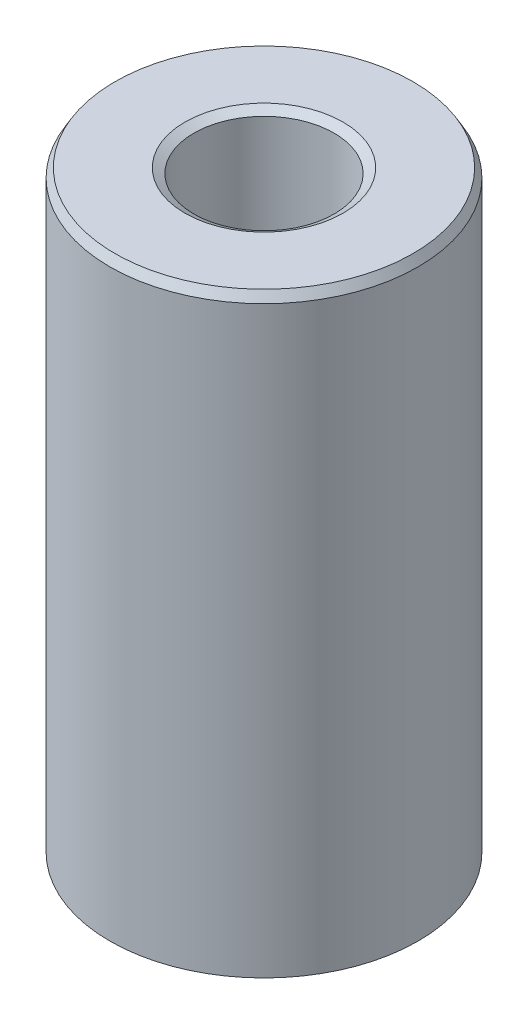
SolidWorks part; units mm, degrees
ref_plane "Front Plane" through (0, 0, 0) normal (0, 0, 1) x (1, 0, 0)
ref_plane "Top Plane" through (0, 0, 0) normal (0, 1, 0) x (1, 0, 0)
ref_plane "Right Plane" through (0, 0, 0) normal (1, 0, 0) x (0, 0, -1)
sketch "Sketch1" plane through (0, 0, 0) normal (0, 1, 0) x (1, 0, 0)
  circle A0 centre (0, 0) radius 60
  dimension "SLEEVE_OD" = 120
extrude "Boss-Extrude1" add sketch "Sketch1" along normal blind 232.8136
sketch "Sketch2" plane through (0, 0, 0) normal (0, 1, 0) x (1, 0, 0)
  circle A0 centre (0, 0) radius 27.3008
  dimension "BORE_D" = 54.6017
extrude "Cut-Extrude1" cut sketch "Sketch2" along normal through all
chamfer "Chamfer1" distance 3.4648 angle 30 4 edges at (0, 232.8136, 27.3008) (0, 0, 27.3008) (0, 0, 60) (0, 232.8136, 60) first distance on face at (0, 232.8136, 27.3008) first distance on face at (0, 0, 27.3008) first distance on face at (0, 232.8136, 60)
